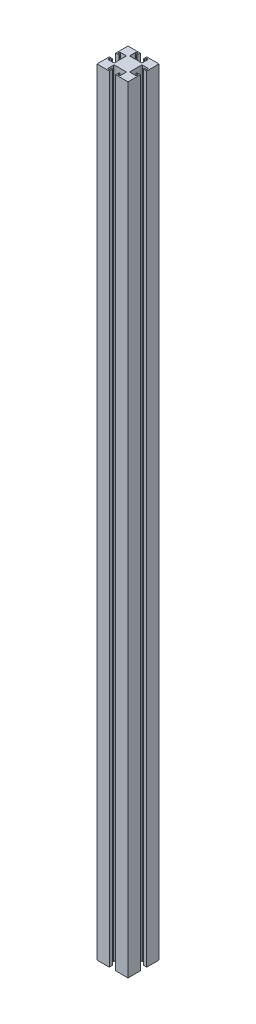
SolidWorks part; units mm, degrees
ref_plane "Plano frontal" through (0, 0, 0) normal (0, 0, 1) x (1, 0, 0)
ref_plane "Plano superior" through (0, 0, 0) normal (0, 1, 0) x (1, 0, 0)
ref_plane "Plano direito" through (0, 0, 0) normal (1, 0, 0) x (0, 0, -1)
sketch "Esboço2" plane through (0, 0, 0) normal (0, 1, 0) x (1, 0, 0)
  line L0 (-1.8037, 6.5679) -> (2.6963, 6.5679)
  line L1 (-1.8037, -17.5821) -> (38.1963, -17.5821)
  line L2 (-1.8037, -17.5821) -> (-1.8037, 22.4179)
  line L3 (-1.8037, 22.4179) -> (38.1963, 22.4179)
  line L4 (38.1963, -17.5821) -> (38.1963, 22.4179)
  line L5 (2.6963, 6.5679) -> (2.6963, 7.9179)
  line L6 (2.2188, 10.4179) -> (7.2188, 10.4179)
  line L7 (8.2188, 9.4179) -> (8.2188, -4.5821)
  line L8 (7.2188, -5.5821) -> (2.2188, -5.5821)
  line L9 (2.2188, -5.5821) -> (0.7188, -5.5821)
  line L10 (2.6963, -1.7321) -> (-1.8037, -1.7321)
  line L11 (0.7188, 10.4179) -> (2.2188, 10.4179)
  line L12 (2.6963, -1.7321) -> (2.6963, -3.0821)
  line L13 (2.6963, 7.9179) -> (-0.2812, 7.9179)
  line L14 (-0.2812, 7.9179) -> (-0.2812, 9.4179)
  line L15 (2.6963, -3.0821) -> (-0.2812, -3.0821)
  line L16 (-0.2812, -3.0821) -> (-0.2812, -4.5821)
  line L17 (-1.8037, 6.5679) -> (-1.8037, -1.7321)
  line L18 (18.1963, 22.4179) -> (18.1963, -17.5821) construction
  line L19 (-1.8037, 2.4179) -> (38.1963, 2.4179) construction
  line L20 (38.1963, 6.5679) -> (38.1963, -1.7321)
  line L21 (36.6737, -3.0821) -> (36.6737, -4.5821)
  line L22 (33.6963, -3.0821) -> (36.6737, -3.0821)
  line L23 (36.6737, 7.9179) -> (36.6737, 9.4179)
  line L24 (33.6963, 7.9179) -> (36.6737, 7.9179)
  line L25 (33.6963, -1.7321) -> (33.6963, -3.0821)
  line L26 (35.6737, 10.4179) -> (34.1737, 10.4179)
  line L27 (33.6963, -1.7321) -> (38.1963, -1.7321)
  line L28 (34.1737, -5.5821) -> (35.6737, -5.5821)
  line L29 (29.1737, -5.5821) -> (34.1737, -5.5821)
  line L30 (28.1737, 9.4179) -> (28.1737, -4.5821)
  line L31 (34.1737, 10.4179) -> (29.1737, 10.4179)
  line L32 (33.6963, 6.5679) -> (33.6963, 7.9179)
  line L33 (38.1963, 6.5679) -> (33.6963, 6.5679)
  arc A0 (0.7188, 10.4179) -> (-0.2812, 9.4179) centre (0.7188, 9.4179) ccw
  arc A1 (0.7188, -5.5821) -> (-0.2812, -4.5821) centre (0.7188, -4.5821) cw
  arc A2 (8.2188, 9.4179) -> (7.2188, 10.4179) centre (7.2188, 9.4179) ccw
  arc A3 (7.2188, -5.5821) -> (8.2188, -4.5821) centre (7.2188, -4.5821) ccw
  arc A4 (29.1737, -5.5821) -> (28.1737, -4.5821) centre (29.1737, -4.5821) cw
  arc A5 (28.1737, 9.4179) -> (29.1737, 10.4179) centre (29.1737, 9.4179) cw
  arc A6 (35.6737, -5.5821) -> (36.6737, -4.5821) centre (35.6737, -4.5821) ccw
  arc A7 (35.6737, 10.4179) -> (36.6737, 9.4179) centre (35.6737, 9.4179) cw
  point P22 (-0.2812, -5.5821)
  point P25 (8.2188, 10.4179)
  point P28 (8.2188, -5.5821)
  point P29 (-1.8037, 2.4179)
  point P30 (-1.8037, 2.4179)
  point P57 (28.1737, -5.5821)
  point P58 (28.1737, 10.4179)
  point P59 (36.6737, -5.5821)
  point P60 (0, 0)
  point P61 (0, 0)
  point P62 (18.1963, -17.5821)
  point P82 (0, 0)
  point P83 (0, 0)
  point P84 (0, 0)
  line B0 (14.0463, -17.5821) -> (14.0463, -13.0821)
  line B1 (14.0463, -13.0821) -> (12.6963, -13.0821)
  line B2 (10.1963, -13.5595) -> (10.1963, -8.5595)
  line B3 (11.1963, -7.5595) -> (25.1963, -7.5595)
  line B4 (26.1963, -8.5595) -> (26.1963, -13.5595)
  line B5 (26.1963, -13.5595) -> (26.1963, -15.0595)
  line B6 (22.3463, -13.0821) -> (22.3463, -17.5821)
  line B7 (10.1963, -15.0595) -> (10.1963, -13.5595)
  line B8 (22.3463, -13.0821) -> (23.6963, -13.0821)
  line B9 (12.6963, -13.0821) -> (12.6963, -16.0595)
  line B10 (12.6963, -16.0595) -> (11.1963, -16.0595)
  line B11 (23.6963, -13.0821) -> (23.6963, -16.0595)
  line B12 (23.6963, -16.0595) -> (25.1963, -16.0595)
  line B13 (14.0463, -17.5821) -> (22.3463, -17.5821)
  arc B14 (10.1963, -15.0595) -> (11.1963, -16.0595) centre (11.1963, -15.0595) ccw
  arc B15 (26.1963, -15.0595) -> (25.1963, -16.0595) centre (25.1963, -15.0595) cw
  arc B16 (11.1963, -7.5595) -> (10.1963, -8.5595) centre (11.1963, -8.5595) ccw
  arc B17 (26.1963, -8.5595) -> (25.1963, -7.5595) centre (25.1963, -8.5595) ccw
  line B18 (14.0463, 22.4179) -> (14.0463, 17.9179)
  line B19 (14.0463, 17.9179) -> (12.6963, 17.9179)
  line B20 (10.1963, 18.3954) -> (10.1963, 13.3954)
  line B21 (11.1963, 12.3954) -> (25.1963, 12.3954)
  line B22 (26.1963, 13.3954) -> (26.1963, 18.3954)
  line B23 (26.1963, 18.3954) -> (26.1963, 19.8954)
  line B24 (22.3463, 17.9179) -> (22.3463, 22.4179)
  line B25 (10.1963, 19.8954) -> (10.1963, 18.3954)
  line B26 (22.3463, 17.9179) -> (23.6963, 17.9179)
  line B27 (12.6963, 17.9179) -> (12.6963, 20.8954)
  line B28 (12.6963, 20.8954) -> (11.1963, 20.8954)
  line B29 (23.6963, 17.9179) -> (23.6963, 20.8954)
  line B30 (23.6963, 20.8954) -> (25.1963, 20.8954)
  line B31 (14.0463, 22.4179) -> (22.3463, 22.4179)
  arc B32 (10.1963, 19.8954) -> (11.1963, 20.8954) centre (11.1963, 19.8954) cw
  arc B33 (26.1963, 19.8954) -> (25.1963, 20.8954) centre (25.1963, 19.8954) ccw
  arc B34 (11.1963, 12.3954) -> (10.1963, 13.3954) centre (11.1963, 13.3954) cw
  arc B35 (26.1963, 13.3954) -> (25.1963, 12.3954) centre (25.1963, 13.3954) cw
  dimension "D8" = 2.5
  dimension "D10" = 1
  dimension "D11" = 1
  dimension "D12" = 1
  dimension "D1" = 40
  dimension "D2" = 40
  dimension "D3" = 8.3
  dimension "D4" = 6
  dimension "D5" = 4.5
  dimension "D6" = 1.35
  dimension "D7" = 16
  dimension "D9" = 2.5
sketch_block_instance "Bloco1-1"
sketch_block "Bloco1" parameters "D2"=1, "D3"=1, "D1"=2.5
sketch_block_instance "Bloco1-2"
extrude "Ressalto-extrusão1" add sketch "Esboço2" along normal blind 1000 contours B22 B35 B21 B34 B20 B25 B32 B28 B27 B19 B18 L3 L2 L0 L5 L13 L14 A0 L11 L6 A2 L7 A3 L8 L9 A1 L16 L15 L12 L10 L1 B0 B1 B9 B10 B14 B7 B2 B16 B3 B17 B4 B5 B15 B12 B11 B8 B6 L4 region at (18.1963, 0, -2.4179)
